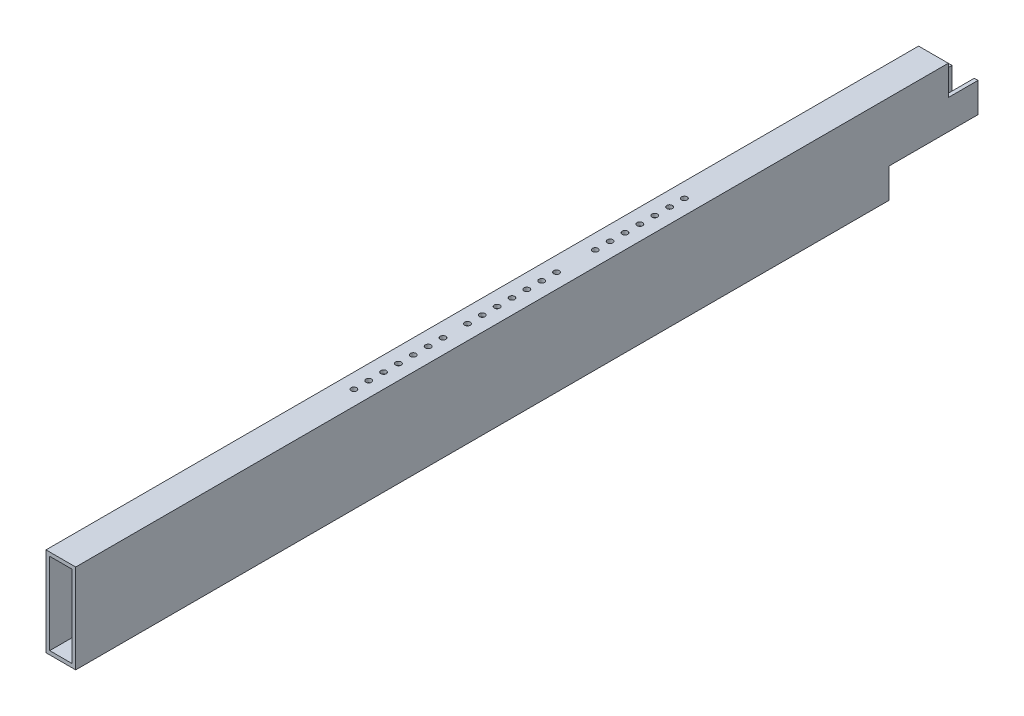
SolidWorks part; units mm, degrees
ref_plane "Front Plane" through (0, 0, 0) normal (0, 0, 1) x (1, 0, 0)
ref_plane "Top Plane" through (0, 0, 0) normal (0, 1, 0) x (1, 0, 0)
ref_plane "Right Plane" through (0, 0, 0) normal (1, 0, 0) x (0, 0, -1)
sketch "Sketch1" plane through (0, 0, 0) normal (0, 0, 1) x (1, 0, 0)
  line L1 (-12.7, -38.1) -> (12.7, -38.1)
  line L2 (-12.7, -38.1) -> (-12.7, 38.1)
  line L3 (-12.7, 38.1) -> (12.7, 38.1)
  line L4 (12.7, -38.1) -> (12.7, 38.1)
  line L5 (-12.7, -38.1) -> (12.7, 38.1) construction
  line L6 (-12.7, 38.1) -> (12.7, -38.1) construction
  point P0 (0, 0)
  dimension "D1" = 25.4
  dimension "D2" = 76.2
extrude "Boss-Extrude1" add sketch "Sketch1" along normal mid plane 771.398
shell "Shell1" thickness 3.175 removed face at (0, 0, -385.699) removed face at (0, 0, 385.699)
sketch "Sketch2" plane through (12.7, 0, 0) normal (1, 0, 0) x (0, 0, -1)
  line L1 (385.699, -38.1) -> (309.499, -38.1)
  line L2 (385.699, -38.1) -> (385.699, -12.7)
  line L3 (385.699, -12.7) -> (309.499, -12.7)
  line L4 (309.499, -38.1) -> (309.499, -12.7)
  dimension "D1" = 25.4
  dimension "D2" = 76.2
extrude "Cut-Extrude1" cut sketch "Sketch2" against normal through all
sketch "Sketch3" plane through (12.7, 0, 0) normal (1, 0, 0) x (0, 0, -1)
  line L1 (385.699, 38.1) -> (360.299, 38.1)
  line L2 (385.699, 38.1) -> (385.699, 12.7)
  line L3 (385.699, 12.7) -> (360.299, 12.7)
  line L4 (360.299, 38.1) -> (360.299, 12.7)
  dimension "D1" = 25.4
extrude "Cut-Extrude2" cut sketch "Sketch3" against normal through all
sketch "Sketch4" plane through (0, 38.1, 0) normal (0, 1, 0) x (1, 0, 0)
  line L0 (-12.7, 360.299) -> (12.7, 360.299) construction
  circle A0 centre (0, 147.3945) radius 2.3812
  circle A1 centre (0, 134.6945) radius 2.3812
  circle A2 centre (0, 121.9945) radius 2.3812
  circle A3 centre (0, 109.2945) radius 2.3812
  circle A4 centre (0, 96.5945) radius 2.3812
  circle A5 centre (0, 83.8945) radius 2.3812
  circle A6 centre (0, 71.1945) radius 2.3812
  circle A7 centre (0, 38.0987) radius 2.3812
  circle A8 centre (0, 25.3987) radius 2.3813
  circle A9 centre (0, 12.6987) radius 2.3813
  circle A10 centre (0, -0.0013) radius 2.3813
  circle A11 centre (0, -12.7013) radius 2.3812
  circle A12 centre (0, -25.4013) radius 2.3812
  circle A13 centre (0, -38.1013) radius 2.3812
  circle A15 centre (0, -58.9932) radius 2.3812
  circle A16 centre (0, -71.6932) radius 2.3812
  circle A17 centre (0, -84.3932) radius 2.3812
  circle A18 centre (0, -97.0932) radius 2.3812
  circle A19 centre (0, -109.7932) radius 2.3812
  circle A20 centre (0, -122.4932) radius 2.3812
  circle A21 centre (0, -135.1932) radius 2.3813
  point P33 (0, 360.299)
  dimension "D1" = 4.7625
  dimension "D3" = 12.7
  dimension "D4" = 12.7
  dimension "D5" = 12.7
  dimension "D6" = 12.7
  dimension "D7" = 12.7
  dimension "D8" = 12.7
  dimension "D9" = 322.2003
  dimension "D10" = 12.7
  dimension "D11" = 12.7
  dimension "D12" = 12.7
  dimension "D13" = 12.7
  dimension "D14" = 12.7
  dimension "D15" = 12.7
  dimension "D16" = 12.7
  dimension "D17" = 419.2922
  dimension "D18" = 12.7
  dimension "D19" = 12.7
  dimension "D20" = 12.7
  dimension "D21" = 12.7
  dimension "D22" = 12.7
  dimension "D2" = 212.9045
extrude "Cut-Extrude3" cut sketch "Sketch4" against normal up to next
